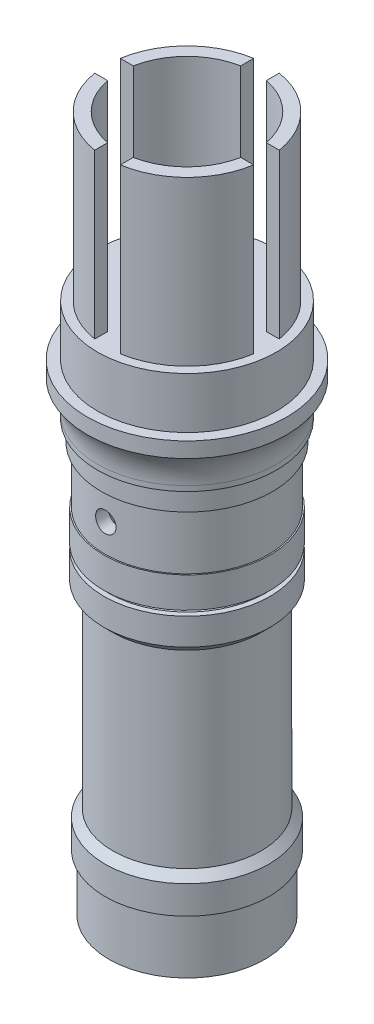
SolidWorks part; units mm, degrees
ref_plane "Alzado" through (0, 0, 0) normal (0, 0, 1) x (1, 0, 0)
ref_plane "Planta" through (0, 0, 0) normal (0, 1, 0) x (1, 0, 0)
ref_plane "Vista lateral" through (0, 0, 0) normal (1, 0, 0) x (0, 0, -1)
sketch "Croquis1" plane through (0, 0, 0) normal (1, 0, 0) x (0, 0, -1)
  line L0 (0, 0) -> (-15.25, 0)
  line L1 (-15.25, 0) -> (-15.25, 11)
  line L2 (-15.25, 11) -> (-16, 11)
  line L3 (-16, 11) -> (-16, 16)
  line L4 (-16, 16) -> (-14.5, 16)
  line L5 (-14.5, 16) -> (-14.5, 57)
  line L6 (-14.5, 57) -> (-16.25, 57)
  line L7 (-16.25, 57) -> (-16.25, 62)
  line L8 (-16.25, 62) -> (-14.75, 62)
  line L9 (-14.75, 62) -> (-14.75, 63)
  line L10 (-14.75, 63) -> (-16.25, 63)
  line L11 (-16.25, 63) -> (-16.25, 69)
  line L12 (-16.25, 69) -> (-16, 69)
  line L13 (-16, 69) -> (-16, 80)
  line L14 (-16.75, 80) -> (-16.75, 84)
  line L15 (-16.75, 84) -> (-17.5, 84)
  line L16 (-17.5, 84) -> (-17.5, 91)
  line L17 (-16.75, 80) -> (-16, 80)
  line L18 (-17.5, 91) -> (-19.5, 91)
  line L19 (-19.5, 91) -> (-19.5, 94)
  line L20 (-19.5, 94) -> (-17.5, 94)
  line L21 (-17.5, 94) -> (-17.5, 104)
  line L22 (-17.5, 104) -> (-15.75, 104)
  line L23 (-15.75, 104) -> (-15.75, 136)
  line L24 (-15.75, 136) -> (0, 136)
  line L25 (0, 136) -> (0, 0)
  dimension "D1" = 15.25
  dimension "D2" = 11
  dimension "D3" = 5
  dimension "D4" = 41
  dimension "D5" = 5
  dimension "D6" = 6
  dimension "D7" = 1
  dimension "D8" = 0.25
  dimension "D9" = 1.5
  dimension "D10" = 1.5
  dimension "D11" = 1.75
  dimension "D12" = 1.5
  dimension "D13" = 0.75
  dimension "D14" = 11
  dimension "D15" = 4
  dimension "D16" = 7
  dimension "D17" = 0.75
  dimension "D18" = 0.75
  dimension "D19" = 3
  dimension "D20" = 10
  dimension "D21" = 32
  dimension "D22" = 1.75
  dimension "D23" = 2
revolve "Revolución1" add sketch "Croquis1" angle 360 about L25
sketch "Croquis2" plane through (0, 0, 0) normal (1, 0, 0) x (0, 0, -1)
  line L0 (17.5, 104) -> (-17.5, 104) construction
  line L1 (-2.5, 104) -> (2.5, 104)
  line L2 (-2.5, 104) -> (-2.5, 143.4158)
  line L3 (-2.5, 143.4158) -> (2.5, 143.4158)
  line L4 (2.5, 104) -> (2.5, 143.4158)
  line L5 (0, 94) -> (0, 104) construction
  line L6 (19.5, 94) -> (-19.5, 94) construction
  dimension "D1" = 5
extrude "Cortar-Extruir1" cut sketch "Croquis2" against normal mid plane 45
pattern_circular "MatrizC2" count 3 over 180 about axis through (0, 136, 0) along (0, 1, 0) of "Cortar-Extruir1" reverse direction yes
sketch "Croquis3" plane through (0, 136, 0) normal (0, 1, 0) x (1, 0, 0)
  circle A0 centre (0, 0) radius 13.25
  dimension "D1" = 26.5
extrude "Cortar-Extruir2" cut sketch "Croquis3" against normal up to surface (32 mm away) up to face at (7.554, 104, 7.554)
fillet "Redondeo2" radius 10 1 edges at (0, 91, 17.5)
chamfer "Chaflán1" distance 0.5 angle 45 3 edges at (0, 11, 15.25) (0, 62, 14.75) (0, 63, 14.75)
chamfer "Chaflán2" distance 2 angle 45 2 edges at (0, 16, 14.5) (0, 57, 14.5)
sketch "Croquis4" plane through (0, 0, 0) normal (0, -1, 0) x (1, 0, 0)
  circle A0 centre (0, 0) radius 13.5
  circle A1 centre (0, 0) radius 9
  dimension "D1" = 18
  dimension "D2" = 27
extrude "Cortar-Extruir3" cut sketch "Croquis4" against normal through all contours A1 region at (0, 0, 0)
extrude "Cortar-Extruir4" cut sketch "Croquis4<3>" against normal offset from surface (97 mm away) 7 contours A0 A1 region at (-13.1182, 0, 0) up to face at (0, 104, 9)
sketch "Croquis4<3>" plane through (0, 0, 0) normal (0, -1, 0) x (1, 0, 0) same geometry as "Croquis4"
sketch "Croquis6" plane through (0, 0, 0) normal (1, 0, 0) x (0, 0, -1)
  line L0 (16, 79.5) -> (13.7666, 79)
  line L1 (16, 69) -> (16, 80) construction
  line L2 (13.7666, 79) -> (3.7666, 79)
  line L3 (3.7666, 79) -> (3.7666, 76.5)
  line L4 (3.7666, 76.5) -> (-16, 76.5)
  line L5 (-16, 80) -> (-16, 69) construction
  line L6 (-16, 76.5) -> (-16, 74.5)
  line L7 (-16, 80) -> (-16, 69) construction
  line L8 (-16, 74.5) -> (16, 74.5)
  line L9 (16, 69) -> (16, 80) construction
  line L10 (16, 74.5) -> (16, 79.5)
  dimension "D1" = 5
  dimension "D2" = 4.5
  dimension "D3" = 2
  dimension "D4" = 10
revolve "Cortar-Revolución1" cut sketch "Croquis6" angle 360 about L8
